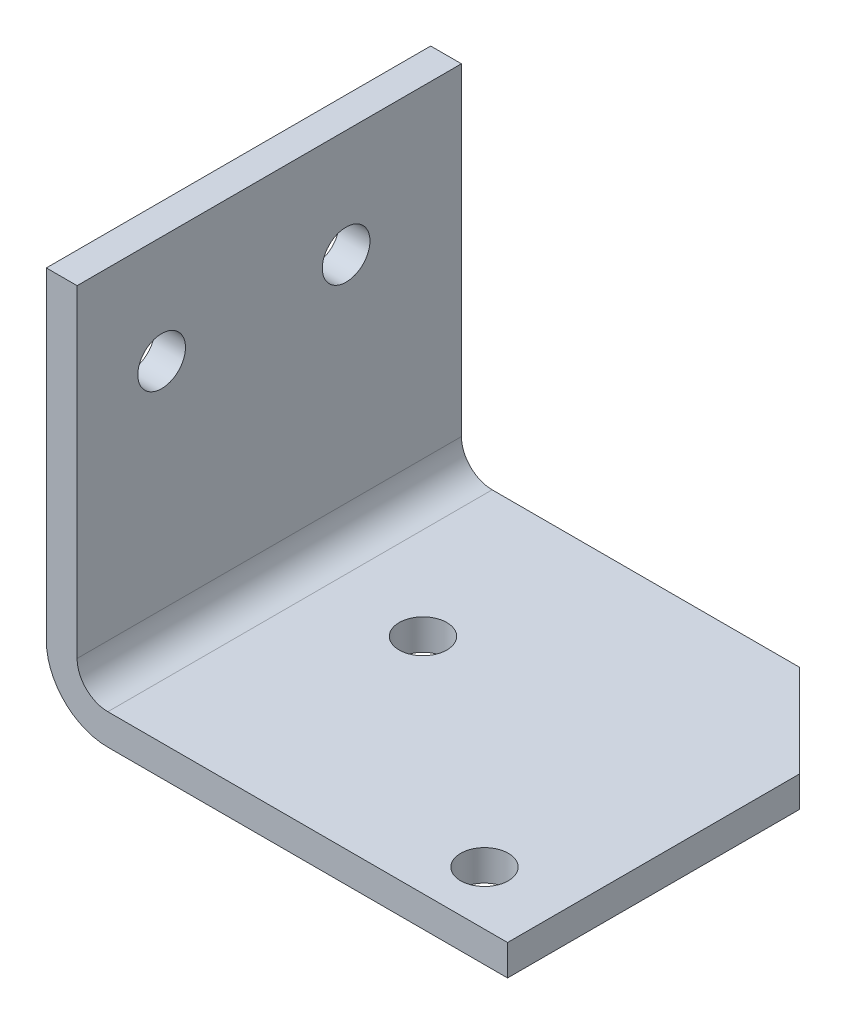
SolidWorks part; units mm, degrees
material "6061 Alloy"
ref_plane "Спереди" through (0, 0, 0) normal (0, 0, 1) x (1, 0, 0)
ref_plane "Сверху" through (0, 0, 0) normal (0, 1, 0) x (1, 0, 0)
ref_plane "Справа" through (0, 0, 0) normal (1, 0, 0) x (0, 0, -1)
sketch "Sketch1" plane through (0, 0, 0) normal (0, 0, 1) x (1, 0, 0)
  line L0 (0, 0) -> (30, 0)
  line L1 (30, 0) -> (30, 2)
  line L2 (30, 2) -> (2, 2)
  line L3 (2, 2) -> (2, 25)
  line L4 (2, 25) -> (0, 25)
  line L5 (0, 25) -> (0, 0)
  dimension "D1" = 30
  dimension "D2" = 25
  dimension "D3" = 2
  dimension "D4" = 2
extrude "Base" add sketch "Sketch1" along normal blind 25
sketch "Sketch2" plane through (0, 0, 0) normal (-1, 0, 0) x (0, 0, 1)
  line L0 (25, 25) -> (25, 0) construction
  line L2 (25, 0) -> (0, 0) construction
  circle A0 centre (19.5, 18) radius 1.55
  circle A1 centre (7.5, 18) radius 1.55
  dimension "D5" = 3.1
  dimension "D1" = 12
  dimension "D2" = 5.5
  dimension "D3" = 18
extrude "Cut-Extrude1" cut sketch "Sketch2" against normal up to surface (2 mm away) up to face at (2, 13.5, 12.5)
sketch "Sketch4" plane through (0, 0, 0) normal (0, -1, 0) x (1, 0, 0)
  line L0 (0, 25) -> (0, 0) construction
  line L1 (0, 0) -> (30, 0) construction
  circle A0 centre (10, 10.5) radius 1.55
  circle A1 centre (25, 21.5) radius 1.55
  dimension "D5" = 3.1
  dimension "D6" = 3.1
  dimension "D1" = 21.5
  dimension "D2" = 10.5
  dimension "D3" = 10
  dimension "D4" = 15
extrude "Cut-Extrude3" cut sketch "Sketch4" against normal through all
chamfer "Chamfer2" distance 6 angle 45 1 edges at (30, 1, 0)
fillet "Fillet1" radius 2 1 edges at (2, 2, 12.5)
fillet "Fillet2" radius 4 1 edges at (0, 0, 12.5)
